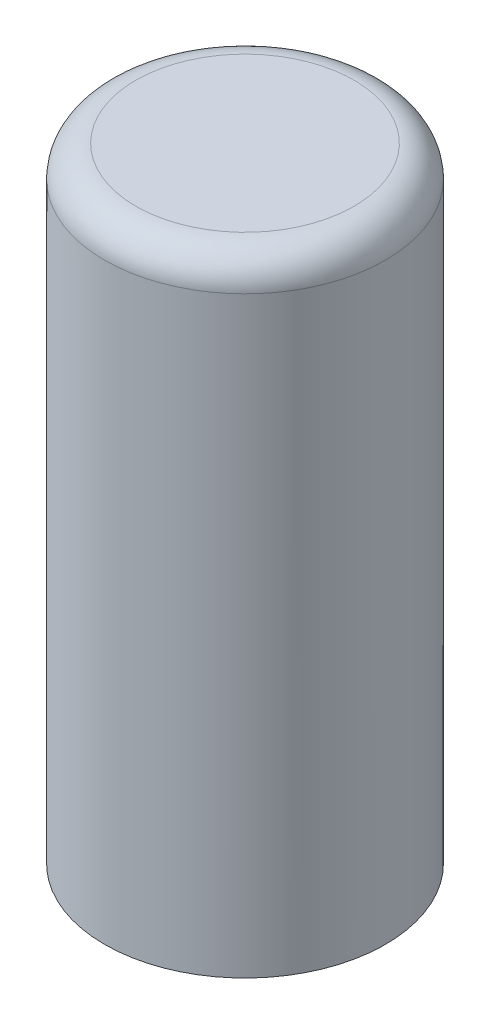
SolidWorks part; units mm, degrees
ref_plane "Front Plane" through (0, 0, 0) normal (0, 0, 1) x (1, 0, 0)
ref_plane "Top Plane" through (0, 0, 0) normal (0, 1, 0) x (1, 0, 0)
ref_plane "Right Plane" through (0, 0, 0) normal (1, 0, 0) x (0, 0, -1)
sketch "Sketch2" plane through (0, 0, 0) normal (0, 1, 0) x (1, 0, 0)
  circle A0 centre (0, 0) radius 3
  circle A1 centre (0, 0) radius 4.5
  dimension "D1" = 1.5
  dimension "D2" = 6
extrude "Boss-Extrude1" add sketch "Sketch2" against normal blind 20
extrude "Boss-Extrude2" add sketch "Sketch2<2>" against normal blind 2 contours A0
sketch "Sketch2<2>" plane through (0, 0, 0) normal (0, 1, 0) x (1, 0, 0) same geometry as "Sketch2"
fillet "Fillet1" radius 1 1 edges at (0, 0, 4.5) first distance on face at (0, -20, 4.5)
